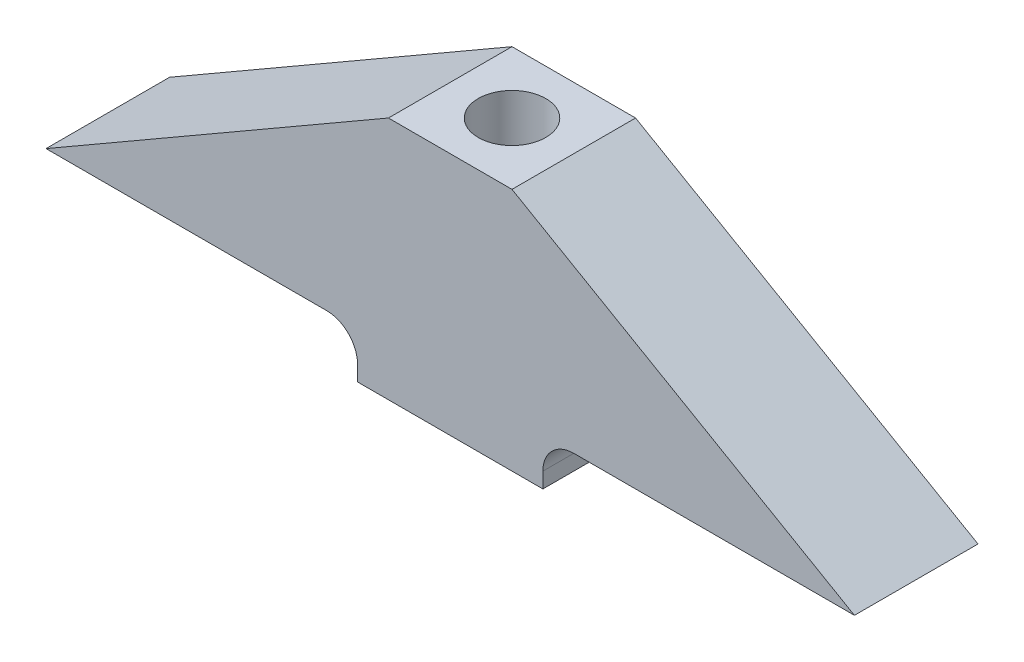
SolidWorks part; units mm, degrees
material "6061-T6 (SS)"
ref_plane "Front Plane" through (0, 0, 0) normal (0, 0, 1) x (1, 0, 0)
ref_plane "Top Plane" through (0, 0, 0) normal (0, 1, 0) x (1, 0, 0)
ref_plane "Right Plane" through (0, 0, 0) normal (1, 0, 0) x (0, 0, -1)
sketch "Sketch1" plane through (0, 0, 0) normal (0, 0, 1) x (1, 0, 0)
  line L0 (0, 0) -> (64.0405, 0)
  line L1 (166.1811, 0) -> (95.7905, 40.64)
  line L2 (95.7905, 40.64) -> (70.3905, 40.64)
  line L3 (70.3905, 40.64) -> (0, 0)
  line L4 (64.0405, 0) -> (64.0405, -9.525)
  line L5 (64.0405, -9.525) -> (102.1405, -9.525)
  line L6 (102.1405, -9.525) -> (102.1405, 0)
  line L7 (102.1405, 0) -> (166.1811, 0)
  point P8 (83.0905, -9.525)
  point P10 (83.0905, 40.64)
  dimension "D1" = 30
  dimension "D2" = 30
  dimension "D3" = 25.4
  dimension "D4" = 40.64
  dimension "D5" = 9.525
  dimension "D6" = 38.1
extrude "Boss-Extrude1" add sketch "Sketch1" along normal blind 25.4
hole_wizard "35/64 (0.54688) Diameter Hole1" positions "Sketch2" profile "Sketch3" hole size "35/64" standard "ANSI Inch"
sketch "Sketch2" plane through (0, 40.64, 0) normal (0, 1, 0) x (1, 0, 0)
  point P0 (83.0905, -12.7)
  dimension "D1" = 12.7
  dimension "D2" = 12.7
sketch "Sketch3" plane through (83.0905, 40.64, 12.7) normal (1, 0, 0) x (0, 0, 1)
  line L0 (0, 0) -> (0, 39.2252)
  line L1 (0, 39.2252) -> (6.9454, 35.052)
  line L2 (6.9454, 35.052) -> (6.9454, 0)
  line L5 (6.9454, 0) -> (0, 0)
  line L10 (0, 39.2252) -> (-6.9454, 35.052) construction
  line L11 (0, -6.35) -> (0, 107.95) construction
  dimension "Hole Dia." = 13.8908
  dimension "Hole Depth" = 35.052
  dimension "Drill Angle" = 118
hole_wizard "1/4-28 Tapped Hole1" positions "Sketch4" profile "Sketch5" tap size "1/4-28" standard "ANSI Inch"
sketch "Sketch4" plane through (0, -9.525, 0) normal (0, -1, 0) x (-1, 0, 0)
  point P0 (-92.6155, -15.875)
  point P3 (-73.5655, -9.525)
  dimension "D1" = 9.525
  dimension "D2" = 9.525
  dimension "D3" = 9.525
  dimension "D4" = 9.525
sketch "Sketch5" plane through (92.6155, -9.525, 15.875) normal (1, 0, 0) x (0, 0, -1)
  line L0 (0, 0) -> (0, 10.7694)
  line L1 (0, 10.7694) -> (2.7051, 9.144)
  line L2 (2.7051, 9.144) -> (2.7051, 0)
  line L5 (2.7051, 0) -> (0, 0)
  line L10 (0, 10.7694) -> (-2.7051, 9.144) construction
  line L11 (0, -6.35) -> (0, 107.95) construction
  dimension "Tap Drill Dia." = 5.4102
  dimension "Tap Drill Depth" = 9.144
  dimension "Drill Angle" = 118
cosmetic thread "Hole Thread1" parameters "D1"=6.35, "D2"=6.35
cosmetic thread "Hole Thread2" parameters "D1"=6.35, "D2"=6.35
fillet "Fillet1" radius 6.35 2 edges at (102.1405, 0, 12.7) (64.0405, 0, 12.7)
